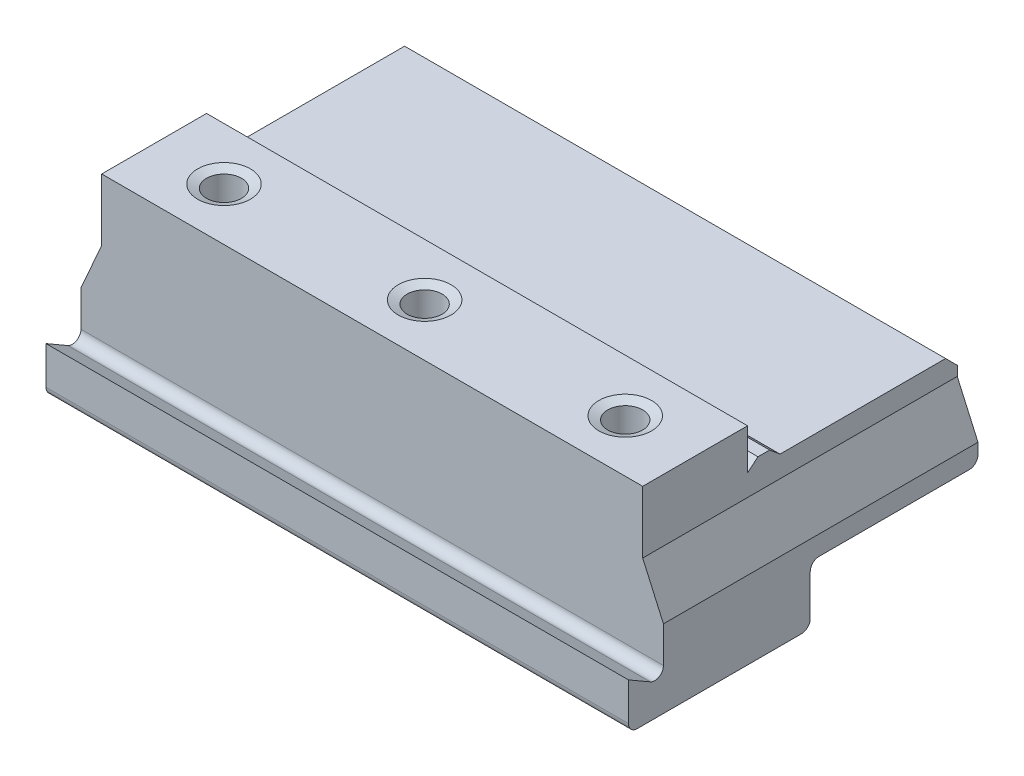
SolidWorks part; units mm, degrees
material "Cast Carbon Steel"
ref_plane "Front Plane" through (0, 0, 0) normal (0, 0, 1) x (1, 0, 0)
ref_plane "Top Plane" through (0, 0, 0) normal (0, 1, 0) x (1, 0, 0)
ref_plane "Right Plane" through (0, 0, 0) normal (1, 0, 0) x (0, 0, -1)
sketch "Sketch1" plane through (0, 0, 0) normal (1, 0, 0) x (0, 0, -1)
  line L0 (-6, -9.25) -> (-6, -15.75)
  line L1 (-4.5, -17.25) -> (23.7, -17.25)
  line L2 (25.2, -15.75) -> (25.2, -8.75)
  line L3 (26.7, -7.25) -> (52.5, -7.25)
  line L4 (54, -5.75) -> (54, 5.75)
  line L5 (54, 5.75) -> (52, 7.75)
  line L6 (52, 7.75) -> (23.5753, 7.75)
  line L7 (23.5753, 7.75) -> (21.7876, 9.25)
  line L8 (21.7876, 9.25) -> (19.7876, 9.25)
  line L9 (19.7876, 9.25) -> (18, 7.75)
  line L10 (18, 7.75) -> (18, 14.75)
  line L11 (18, 14.75) -> (0, 14.75)
  line L12 (0, 14.75) -> (0, -10.116)
  line L13 (-2.25, -11.4151) -> (-6, -9.25)
  line L14 (0, 0) -> (37799.0751, 0) construction
  arc A0 (52.5, -7.25) -> (54, -5.75) centre (52.5, -5.75) ccw
  arc A1 (25.2, -8.75) -> (26.7, -7.25) centre (26.7, -8.75) cw
  arc A2 (23.7, -17.25) -> (25.2, -15.75) centre (23.7, -15.75) ccw
  arc A3 (-6, -15.75) -> (-4.5, -17.25) centre (-4.5, -15.75) ccw
  arc A4 (0, -10.116) -> (-2.25, -11.4151) centre (-1.5, -10.116) cw
  point P17 (54, 0)
  point P18 (21.9808, -31.8462)
  point P19 (20.7876, 9.25)
  point P20 (44.4399, 24.1778)
  point P21 (81.7277, 7.3197)
  point P22 (23.4387, -19.539)
  point P23 (27.439, -22.2534)
  point P24 (24.1531, -8.1097)
  point P25 (79.3903, 12.1452)
  point P26 (50.7545, -12.8901)
  point P27 (79.2739, -6.0286)
  point P36 (-6, -17.25)
  point P37 (76.4308, 8.092)
  point P40 (25.2, -16.405)
  point P41 (54, 7.9349)
  point P42 (51.4135, 10.0432)
  point P43 (18, 17.7288)
  dimension "D13" = 1.5
  dimension "D15" = 1.5
  dimension "D1" = 18
  dimension "D2" = 7
  dimension "D3" = 60
  dimension "D4" = 6
  dimension "D5" = 28.8
  dimension "D6" = 2
  dimension "D7" = 100
  dimension "D8" = 40
  dimension "D9" = 1.5
  dimension "D10" = 60
  dimension "D11" = 32
  dimension "D12" = 8
  dimension "D14" = 45
  dimension "D16" = 15
  dimension "D17" = 2
extrude "Boss-Extrude1" add sketch "Sketch1" along normal blind 100
sketch "Sketch2" plane through (0, 0, 0) normal (0, 0, 1) x (1, 0, 0)
  line L0 (96.4382, 14.75) -> (96.4382, 4.0833)
  line L1 (100, 14.75) -> (0, 14.75) construction
  line L2 (96.4382, 4.0833) -> (100, -3.9167)
  line L3 (100, 14.75) -> (100, -10.116) construction
  line L4 (100, -3.9167) -> (100, 14.75)
  line L5 (100, 14.75) -> (96.4382, 14.75)
  line L6 (50, -17.25) -> (50, 14.75) construction
  line L7 (100, -17.25) -> (0, -17.25) construction
  line L8 (0, 14.75) -> (3.5618, 14.75)
  line L9 (0, -3.9167) -> (0, 14.75)
  line L10 (3.5618, 4.0833) -> (0, -3.9167)
  line L11 (3.5618, 14.75) -> (3.5618, 4.0833)
  dimension "D1" = 24
  dimension "D2" = 10.6667
  dimension "D3" = 8
extrude "Cut-Extrude1" cut sketch "Sketch2" against normal through all both and the other way through all
sketch "Sketch3" plane through (0, 14.75, 0) normal (0, 1, 0) x (1, 0, 0)
  line L5 (96.4382, 18) -> (3.5618, 18) construction
  line L6 (3.5618, 54) -> (3.5618, 0) construction
  line L7 (96.4382, 54) -> (96.4382, 0) construction
  line L8 (96.4382, 0) -> (3.5618, 0) construction
  point P6 (0, 0)
  point P9 (50, 0)
  point P10 (0, 0)
  point P11 (0, 0)
  point P16 (50, 9)
  point P17 (84.4382, 9)
  point P18 (15.5618, 9)
  point P20 (0, 0)
  dimension "D1" = 9
  dimension "D2" = 12
  dimension "D3" = 12
hole_wizard "Ø6.0mm Dowel Hole1" positions "Sketch4" profile "Sketch5" hole size "Ø6.0" standard "ANSI Metric"
sketch "Sketch4" plane through (0, 14.75, 0) normal (0, 1, 0) x (1, 0, 0)
  point P0 (15.5618, 9)
  point P3 (50, 9)
  point P6 (84.4382, 9)
sketch "Sketch5" plane through (15.5618, 14.75, -9) normal (1, 0, 0) x (0, 0, 1)
  line L0 (0, 0) -> (0, 10)
  line L1 (0, 10) -> (3, 8.1974)
  line L2 (3, 8.1974) -> (3, 0.025)
  line L3 (3, 0.025) -> (3.025, 0)
  line L5 (3.025, 0) -> (0, 0)
  line L6 (-3, 0.025) -> (-3.025, 0) construction
  line L10 (0, 10) -> (-3, 8.1974) construction
  line L11 (0, -6.35) -> (0, 107.95) construction
  dimension "Hole Dia." = 6
  dimension "Hole Depth" = 10
  dimension "Near C'Sink Dia." = 6.05
  dimension "Near C'Sink Angle" = 90
  dimension "Drill Angle" = 118
chamfer "Chamfer1" distance 1.5 3 edges at (84.4382, 14.75, -5.975) (50, 14.75, -5.975) (15.5618, 14.75, -5.975)
